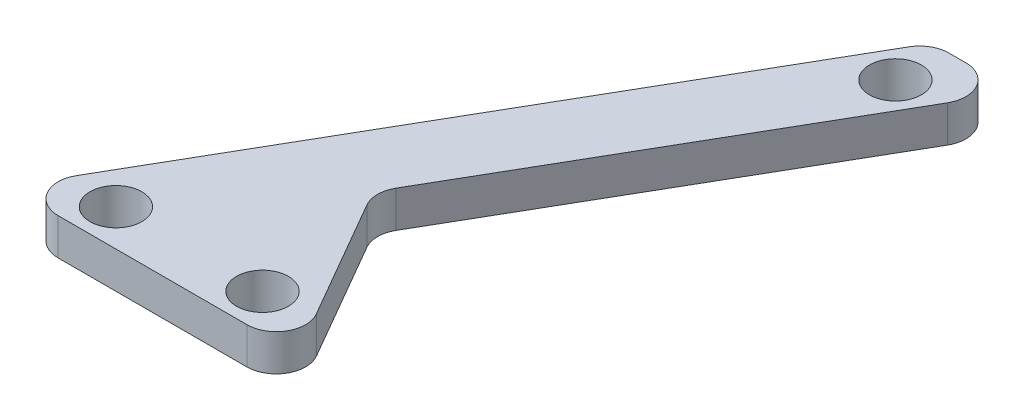
SolidWorks part; units mm, degrees
material "UHMW"
ref_plane "Front Plane" through (0, 0, 0) normal (0, 0, 1) x (1, 0, 0)
ref_plane "Top Plane" through (0, 0, 0) normal (0, 1, 0) x (1, 0, 0)
ref_plane "Right Plane" through (0, 0, 0) normal (1, 0, 0) x (0, 0, -1)
sketch "Sketch1" plane through (0, 0, 0) normal (0, 1, 0) x (1, 0, 0)
  line L0 (14.6647, 25.4) -> (-14.6647, -25.4)
  line L1 (-14.6647, -25.4) -> (10.5003, -25.4)
  line L2 (10.5003, -25.4) -> (1.584, -9.9565)
  line L4 (14.6647, 25.4) -> (21.997, 25.4)
  line L5 (21.997, 25.4) -> (1.584, -9.9565)
  line L6 (-8.4322, -22.225) -> (4.2678, -22.225) construction
  circle A0 centre (-8.4322, -22.225) radius 2.2479
  circle A1 centre (4.2678, -22.225) radius 2.2479
  point P0 (-2.0822, -22.225)
  point P9 (-2.0822, -25.4)
  point P11 (-4.2062, -14.0415)
  point P12 (5.9121, -2.4599)
  point P13 (-4.3786, -15.204)
  point P14 (18.3309, 25.4)
  dimension "D2" = 4.4958
  dimension "D5" = 3.175
  dimension "D1" = 12.7
  dimension "D3" = 60
  dimension "D4" = 60
  dimension "D6" = 6.35
  dimension "D7" = 3.81
  dimension "D8" = 25.4
  dimension "D9" = 50.8
extrude "Boss-Extrude1" add sketch "Sketch1" along normal blind 3.175
sketch "Sketch2" plane through (0, 3.175, 0) normal (0, 1, 0) x (1, 0, 0)
  line L0 (13.0772, 22.6504) -> (18.5765, 19.4754) construction
  line L1 (14.6647, 25.4) -> (-14.6647, -25.4) construction
  line L2 (1.584, -9.9565) -> (21.997, 25.4) construction
  circle A0 centre (15.8268, 21.0629) radius 2.2479
  dimension "D1" = 4.4958
  dimension "D2" = 3.175
extrude "Cut-Extrude1" cut sketch "Sketch2" against normal through all
fillet "Fillet1" radius 2.54 5 edges at (14.6647, 1.5875, -25.4) (21.997, 1.5875, -25.4) (-14.6647, 1.5875, 25.4) (1.584, 1.5875, 9.9565) (10.5003, 1.5875, 25.4)
